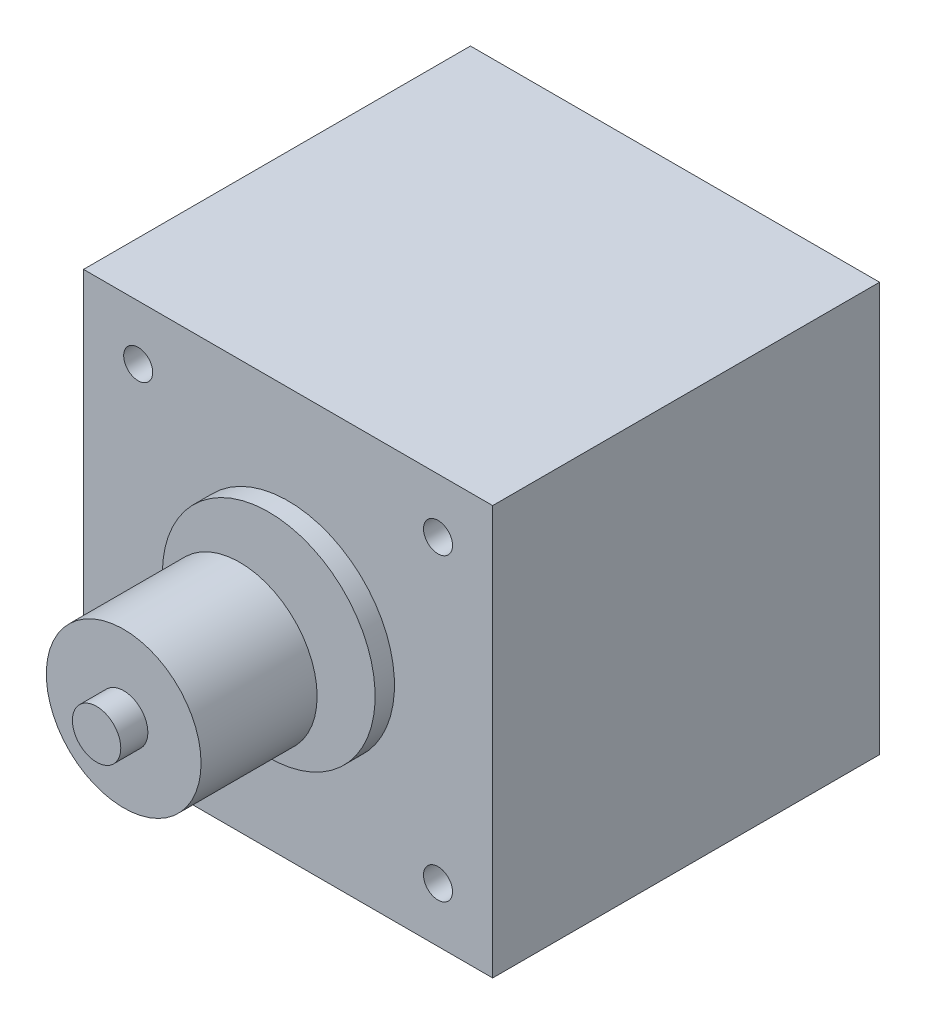
SolidWorks part; units mm, degrees
ref_plane "Спереди" through (0, 0, 0) normal (0, 0, 1) x (1, 0, 0)
ref_plane "Сверху" through (0, 0, 0) normal (0, 1, 0) x (1, 0, 0)
ref_plane "Справа" through (0, 0, 0) normal (1, 0, 0) x (0, 0, -1)
other "Configuration Table"
sketch "Эскиз1" plane through (0, 0, 0) normal (0, 0, 1) x (1, 0, 0)
  line L1 (-21.15, -21.15) -> (21.15, -21.15)
  line L2 (-21.15, -21.15) -> (-21.15, 21.15)
  line L3 (-21.15, 21.15) -> (21.15, 21.15)
  line L4 (21.15, -21.15) -> (21.15, 21.15)
  line L5 (-21.15, -21.15) -> (21.15, 21.15) construction
  line L6 (-21.15, 21.15) -> (21.15, -21.15) construction
  point P0 (0, 0)
  dimension "D1" = 42.3
  dimension "D2" = 42.3
extrude "Корпус" add sketch "Эскиз1" along normal blind 40
sketch "Эскиз2" plane through (0, 0, 0) normal (0, 0, 1) x (1, 0, 0)
  circle A0 centre (0, 0) radius 2.5
extrude "Вал_ПРЕДВ" add sketch "Эскиз2" along normal blind 59.8
sketch "Эскиз3" plane through (0, 0, 0) normal (0, 0, 1) x (1, 0, 0)
  circle A0 centre (0, 0) radius 11
  dimension "D1" = 22
extrude "Буртик_ПРЕДВ" add sketch "Эскиз3" along normal blind 42
sketch "Эскиз4" plane through (0, 0, 0) normal (0, 0, 1) x (1, 0, 0)
  circle A0 centre (0, 0) radius 8
  dimension "D1" = 16
extrude "Шкив_габарит_ПРЕДВ" add sketch "Эскиз4" along normal blind 12 from offset 45
sketch "Эскиз5" plane through (0, 0, 0) normal (0, 0, 1) x (1, 0, 0)
  circle A0 centre (-15.5, -15.5) radius 1.5
  circle A1 centre (-15.5, 15.5) radius 1.5
  circle A2 centre (15.5, -15.5) radius 1.5
  circle A3 centre (15.5, 15.5) radius 1.5
  dimension "D1" = 3
  dimension "D2" = 3
  dimension "D3" = 3
  dimension "D4" = 3
extrude "Крепеж_М3_ПРЕДВ" cut sketch "Эскиз5" against normal blind 4.5 from offset 40
equation "\"Мотор X ширина корпуса\"= 42.3"
equation "\"Мотор X высота корпуса\"= 42.3"
equation "\"Мотор X длина корпуса\"= 40"
equation "\"Мотор X вылет вала\"= 19.8"
equation "\"Мотор Y ширина корпуса\"= 42.3"
equation "\"Мотор Y высота корпуса\"= 42.3"
equation "\"Мотор Y длина корпуса\"= 48"
equation "\"Мотор Y вылет вала\"= 30"
equation "\"Мотор Z ширина корпуса\"= 42"
equation "\"Мотор Z высота корпуса\"= 42"
equation "\"Мотор Z длина корпуса\"= 40"
equation "\"Мотор Z вылет вала\"= 23"
equation "\"Мотор диаметр вала ПРЕДВ\"= 5"
equation "\"Мотор шаг крепления ПРЕДВ\"= 31"
equation "\"Мотор диаметр отверстий ПРЕДВ\"= 3"
equation "\"Мотор глубина отверстий ПРЕДВ\"= 4.5"
equation "\"Мотор диаметр буртика ПРЕДВ\"= 22"
equation "\"Мотор высота буртика ПРЕДВ\"= 2"
equation "\"Мотор диаметр шкива ПРЕДВ\"= 16"
equation "\"Мотор длина шкива ПРЕДВ\"= 12"
equation "\"Мотор отступ шкива ПРЕДВ\"= 5"
equation "\"Мотор X шаг градусов\"= 1.8"
equation "\"Мотор X ток А\"= 1.5"
equation "\"Мотор X сопротивление Ом\"= 1.3"
equation "\"Мотор X индуктивность мГн\"= 2"
equation "\"Мотор Y шаг градусов\"= 1.8"
equation "\"Мотор Y ток А\"= 2.2"
equation "\"Мотор Y сопротивление Ом\"= 0.9"
equation "\"Мотор Y индуктивность мГн\"= 2"
equation "\"Мотор Z шаг градусов\"= 1.8"
equation "\"Мотор Z ток А\"= 1"
equation "\"Мотор Z сопротивление Ом\"= 4"
equation "\"Мотор Z индуктивность мГн\"= 8"
equation "\"Мотор Y диаметр ротора\"= 25.78"
equation "\"D1@Эскиз1\" = \"Мотор X ширина корпуса\""
equation "\"D2@Эскиз1\" = \"Мотор X высота корпуса\""
equation "\"D1@Корпус\" = \"Мотор X длина корпуса\""
equation "\"D1@Эскиз2\" = \"Мотор диаметр вала ПРЕДВ\""
equation "\"D1@Вал_ПРЕДВ\" = \"Мотор X длина корпуса\" + \"Мотор X вылет вала\""
equation "\"D1@Эскиз3\" = \"Мотор диаметр буртика ПРЕДВ\""
equation "\"D1@Буртик_ПРЕДВ\" = \"Мотор X длина корпуса\" + \"Мотор высота буртика ПРЕДВ\""
equation "\"D1@Эскиз4\" = \"Мотор диаметр шкива ПРЕДВ\""
equation "\"D1@Шкив_габарит_ПРЕДВ\" = \"Мотор длина шкива ПРЕДВ\""
equation "\"D19@Шкив_габарит_ПРЕДВ\" = \"Мотор X длина корпуса\" + \"Мотор отступ шкива ПРЕДВ\""
equation "\"D1@Эскиз5\" = \"Мотор диаметр отверстий ПРЕДВ\""
equation "\"D2@Эскиз5\" = \"Мотор диаметр отверстий ПРЕДВ\""
equation "\"D3@Эскиз5\" = \"Мотор диаметр отверстий ПРЕДВ\""
equation "\"D4@Эскиз5\" = \"Мотор диаметр отверстий ПРЕДВ\""
equation "\"D1@Крепеж_М3_ПРЕДВ\" = \"Мотор глубина отверстий ПРЕДВ\""
equation "\"D19@Крепеж_М3_ПРЕДВ\" = \"Мотор X длина корпуса\""
equation "\"Ширина груза\"= 420"
equation "\"Глубина груза\"= 490"
equation "\"Высота груза\"= 297"
equation "\"Ширина ячейки\"= \"Ширина груза\" + 10"
equation "\"Глубина ячейки\"= \"Глубина груза\" + 10"
equation "\"Высота ячейки\"= \"Высота груза\" + 10 + 13"
equation "\"Колво ячеек ширина\"= 2"
equation "\"Колво ячеек высота\"= 2"
equation "\"Толщина стенки\"= 10"
equation "\"Крепление дверцы\"= 5"
equation "\"Ширина рейки\"= \"Толщина шестерни\""
equation "\"Высота рейки\"= 20"
equation "\"Высота пола\"= 20"
equation "\"Колво полозьев\"= 5"
equation "\"Отступ рейки\"= 20"
equation "\"Глубина каретки\"= \"Глубина ячейки\" + 80"
equation "\"Отступ шпильки\"= 20"
equation "\"Диаметр шпильки\"= 5"
equation "\"Длинна шпильки\"= ( \"Высота ячейки\" + \"Толщина стенки\" + \"Высота пола\" ) * \"Колво ячеек высота\" + ( \"Толщина стенки\" + \"Отступ рейки\" ) * 2"
equation "\"Ширина пластины\"= 50  "
equation "\"Высота зона выгрузки\"= \"Высота ячейки\" * 2 + \"Толщина стенки\" * 2"
equation "\"Колво выгрузки\"= 1"
equation "\"Отступ крепления мотора фиксации\" = 30"
equation "\"Диаметр оси\"= 10"
equation "\"Диаметр ролика\"= 20"
equation "\"Колво роликов\"= 10"
equation "\"Шаг роликов\"= \"Диаметр ролика\" + 20"
equation "\"Ширина ячейки выгрузки\"= \"Ширина ячейки\" + \"Толщина стенки\" + \"Отступ крепления мотора фиксации\"*2"
equation "\"Длинна рейки\"= ( \"Ширина ячейки\" + \"Толщина стенки\" + \"Крепление дверцы\" ) * \"Колво ячеек ширина\" + \"Ширина ячейки выгрузки\" * \"Колво выгрузки\" + \"Толщина стенки\""
